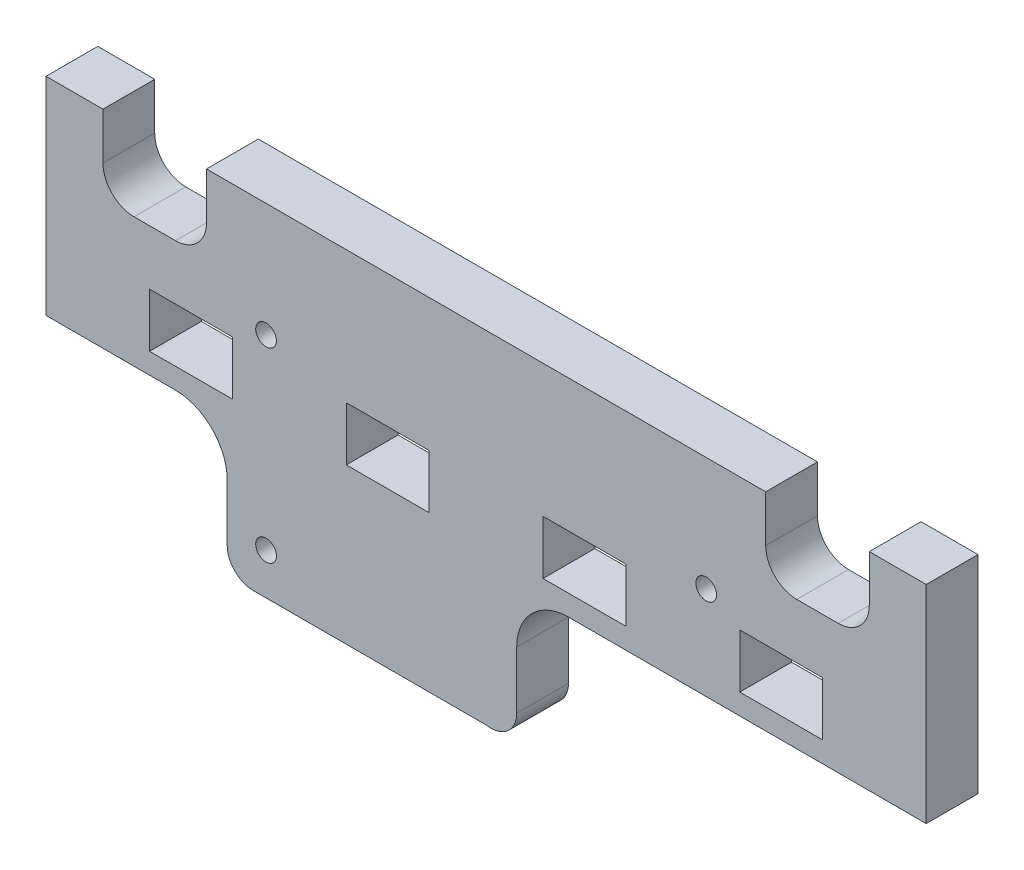
SolidWorks part; units mm, degrees
ref_plane "Front Plane" through (0, 0, 0) normal (0, 0, 1) x (1, 0, 0)
ref_plane "Top Plane" through (0, 0, 0) normal (0, 1, 0) x (1, 0, 0)
ref_plane "Right Plane" through (0, 0, 0) normal (1, 0, 0) x (0, 0, -1)
sketch "Sketch1" plane through (0, 0, 0) normal (0, 0, 1) x (1, 0, 0)
  line L0 (24.4856, 0) -> (59.0288, 0)
  line L1 (-25.9712, 20) -> (59.0288, 20)
  line L2 (-25.9712, 20) -> (-25.9712, 0)
  line L3 (-25.9712, 0) -> (-13.4712, 0)
  line L4 (59.0288, 20) -> (59.0288, 0)
  line L5 (16.5288, 20) -> (16.5288, -13) construction
  line L6 (-8.4712, -5) -> (-8.4712, -10.5)
  line L7 (-5.9712, -13) -> (16.5288, -13)
  line L8 (19.4856, -5) -> (19.4856, -10.5421)
  arc A0 (19.4856, -5) -> (24.4856, 0) centre (24.4856, -5) cw
  arc A1 (-8.4712, -5) -> (-13.4712, 0) centre (-13.4712, -5) ccw
  arc A2 (16.5288, -13) -> (19.4856, -10.5421) centre (16.9856, -10.5421) ccw
  arc A3 (-5.9712, -13) -> (-8.4712, -10.5) centre (-5.9712, -10.5) cw
  point P14 (41.5288, -13)
  point P17 (-8.4712, -13)
  dimension "D4" = 5
  dimension "D5" = 2.5
  dimension "D1" = 85
  dimension "D6" = 20
extrude "Boss-Extrude1" add sketch "Sketch1" along normal blind 5 contours L1 L4 L0 A0 L8 A2 L7 A3 L6 A1 L3 L2
sketch "Sketch2" plane through (0, 0, 5) normal (0, 0, 1) x (1, 0, 0)
  line L0 (-5.9712, 4.6) -> (-25.9712, 4.6) construction
  line L1 (-15.9712, 7.2) -> (-7.9712, 7.2)
  line L2 (-15.9712, 7.2) -> (-15.9712, 2)
  line L3 (-15.9712, 2) -> (-7.9712, 2)
  line L4 (-7.9712, 7.2) -> (-7.9712, 2)
  line L5 (-25.9712, 20) -> (-25.9712, 0) construction
  line L6 (3.0288, 7.2) -> (11.0288, 7.2)
  line L7 (3.0288, 7.2) -> (3.0288, 2)
  line L8 (3.0288, 2) -> (11.0288, 2)
  line L9 (11.0288, 7.2) -> (11.0288, 2)
  line L10 (22.0288, 7.2) -> (30.0288, 7.2)
  line L11 (22.0288, 7.2) -> (22.0288, 2)
  line L12 (22.0288, 2) -> (30.0288, 2)
  line L13 (30.0288, 7.2) -> (30.0288, 2)
  line L14 (41.0288, 7.2) -> (49.0288, 7.2)
  line L15 (41.0288, 7.2) -> (41.0288, 2)
  line L16 (41.0288, 2) -> (49.0288, 2)
  line L17 (49.0288, 7.2) -> (49.0288, 2)
  line L18 (-25.9712, 0) -> (-13.4712, 0) construction
  point P9 (-15.9712, 4.6)
  point P14 (3.0288, 4.6)
  point P19 (22.0288, 4.6)
  point P24 (41.0288, 4.6)
  dimension "D2" = 5.2
  dimension "D3" = 8
  dimension "D4" = 10
  dimension "D5" = 4.6
  dimension "D6" = 11
  dimension "D1" = 4
extrude "Cut-Extrude1" cut sketch "Sketch2" against normal up to next
sketch "Sketch3" plane through (0, 0, 5) normal (0, 0, 1) x (1, 0, 0)
  line L0 (-25.9712, 20) -> (59.0288, 20) construction
  line L1 (-20.4712, 20) -> (-10.4712, 20)
  line L2 (-20.4712, 20) -> (-20.4712, 15.5)
  line L3 (-17.4712, 12.5) -> (-13.4712, 12.5)
  line L4 (-10.4712, 20) -> (-10.4712, 15.5)
  line L5 (-25.9712, 20) -> (-25.9712, 0) construction
  arc A0 (-13.4712, 12.5) -> (-10.4712, 15.5) centre (-13.4712, 15.5) ccw
  arc A1 (-20.4712, 15.5) -> (-17.4712, 12.5) centre (-17.4712, 15.5) ccw
  dimension "D1" = 3
  dimension "D2" = 7.5
  dimension "D3" = 10
  dimension "D4" = 5.5
extrude "Cut-Extrude2" cut sketch "Sketch3" against normal up to next
ref_plane "Plane1" through (16.5288, 0, 0) normal (1, 0, 0) x (0, 0, -1)
mirror "Mirror1" about plane through (16.5288, 0, 0) normal (1, 0, 0) of "Cut-Extrude2"
sketch "Sketch5" plane through (0, 0, 5) normal (0, 0, 1) x (1, 0, 0)
  line L0 (16.5288, 20) -> (16.5288, -13) construction
  line L1 (-10.4712, 20) -> (43.5288, 20) construction
  line L3 (-4.7212, 9) -> (-4.7212, -9) construction
  circle A0 centre (-4.7212, 9) radius 1
  circle A1 centre (37.7788, 9) radius 1
  circle A2 centre (-4.7212, -9) radius 1
  dimension "D2" = 2
  dimension "D1" = 11
  dimension "D3" = 21.25
  dimension "D4" = 18
extrude "Cut-Extrude3" cut sketch "Sketch5" against normal up to next
